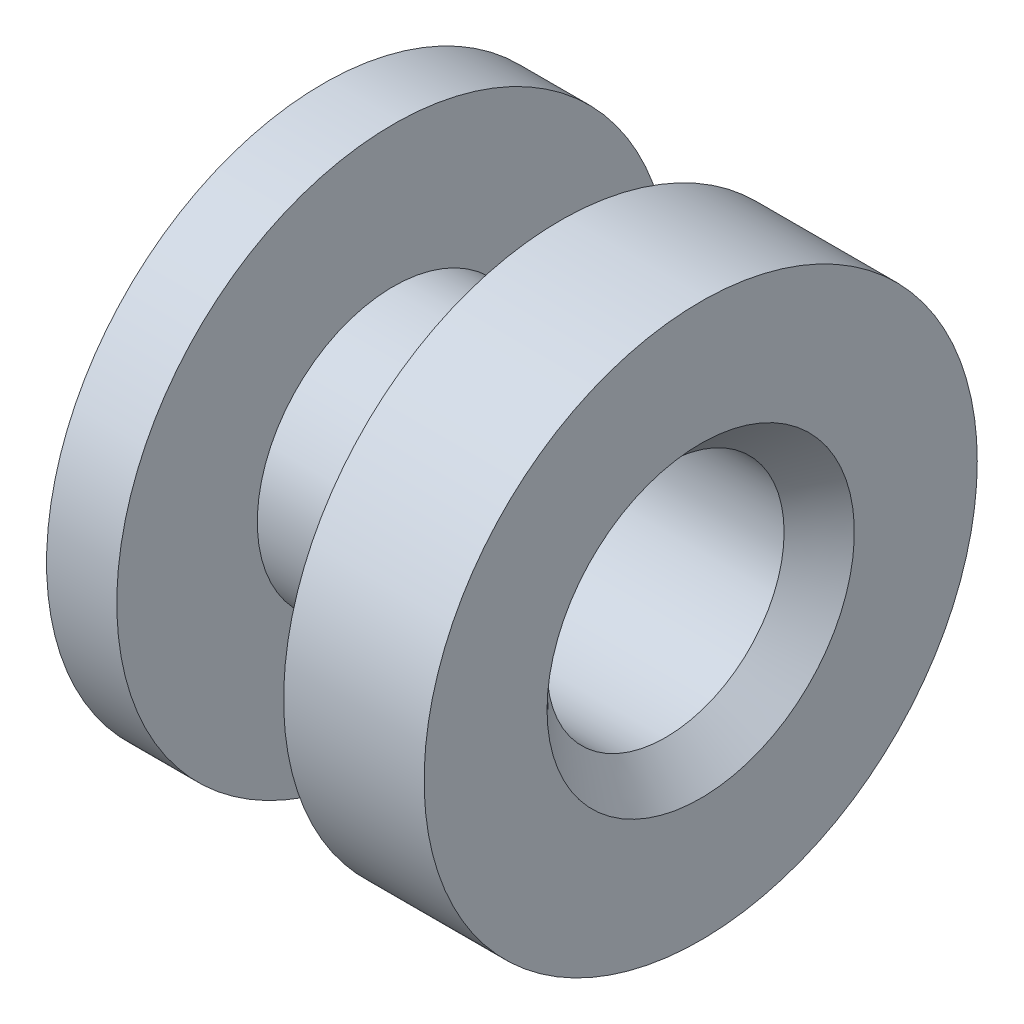
SolidWorks part; units mm, degrees
ref_plane "Front Plane" through (0, 0, 0) normal (0, 0, 1) x (1, 0, 0)
ref_plane "Top Plane" through (0, 0, 0) normal (0, 1, 0) x (1, 0, 0)
ref_plane "Right Plane" through (0, 0, 0) normal (1, 0, 0) x (0, 0, -1)
sketch "Sketch2" plane through (0, 0, 0) normal (0, 0, 1) x (1, 0, 0)
  line L0 (0, 0) -> (0, 8.001)
  line L1 (0, 0) -> (0, 7.874)
  line L2 (0, 8.001) -> (2.032, 8.001)
  line L3 (2.032, 8.001) -> (2.032, 3.937)
  line L4 (2.032, 3.937) -> (6.858, 3.937)
  line L5 (6.858, 3.937) -> (6.858, 8.001)
  line L6 (6.858, 8.001) -> (10.922, 8.001)
  line L7 (10.922, 8.001) -> (10.922, 0)
  line L8 (10.922, 0) -> (0, 0)
revolve "Revolve1" add sketch "Sketch2" angle 360 about L8 region at (5.755, 3.4308, 0)
sketch "Sketch3" plane through (10.922, 0, 0) normal (1, 0, 0) x (0, 0, -1)
  circle A0 centre (0, 0) radius 3.429
extrude "Cut-Extrude1" cut sketch "Sketch3" against normal through all both
chamfer "Chamfer1" distance 1.016 angle 45 1 edges at (10.922, 0, -3.429)
